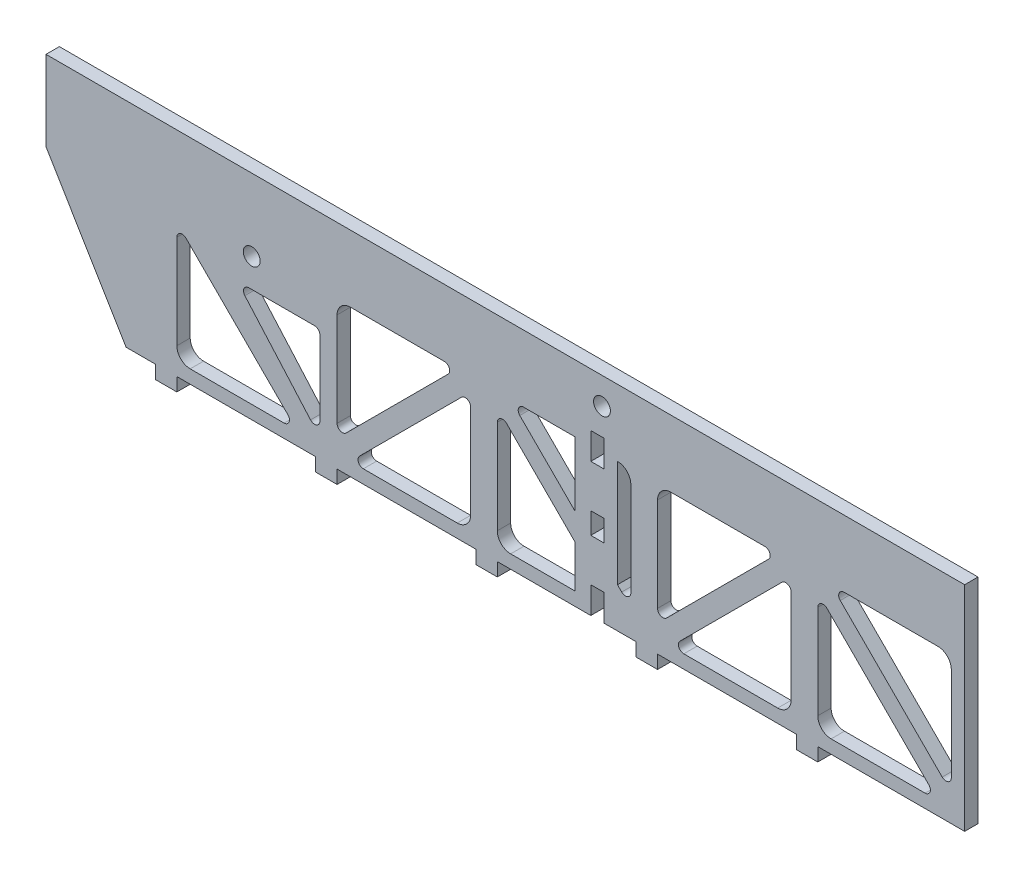
SolidWorks part; units mm, degrees
material "Pine"
ref_plane "Front Plane" through (0, 0, 0) normal (0, 0, 1) x (1, 0, 0)
ref_plane "Top Plane" through (0, 0, 0) normal (0, 1, 0) x (1, 0, 0)
ref_plane "Right Plane" through (0, 0, 0) normal (1, 0, 0) x (0, 0, -1)
sketch "Model" plane through (0, 0, 0) normal (0, 0, 1) x (1, 0, 0)
  line L0 (-306.6281, 15.625) -> (-306.6281, 51.1493)
  line L1 (-309.1681, 53.6893) -> (-340.406, 53.6893)
  line L2 (-342.3135, 49.472) -> (-311.0755, 13.9477)
  line L8 (-171.2321, 6.35) -> (-215.9, 6.35)
  line L9 (-222.25, 57.3679) -> (-222.25, 12.7)
  line L10 (-217.9139, 59.1639) -> (-169.4361, 10.6861)
  line L11 (-234.95, 57.3679) -> (-234.95, 12.7)
  line L12 (-241.3, 6.35) -> (-285.9679, 6.35)
  line L13 (-239.2861, 59.1639) -> (-287.7639, 10.6861)
  line L14 (-294.1139, 17.0361) -> (-245.6361, 65.5139)
  line L15 (-298.45, 63.5) -> (-298.45, 18.8321)
  line L16 (-247.4321, 69.85) -> (-292.1, 69.85)
  line L17 (-323.6321, 6.35) -> (-368.3, 6.35)
  line L18 (-374.65, 57.3679) -> (-374.65, 12.7)
  line L19 (-370.3139, 59.1639) -> (-321.8361, 10.6861)
  line L20 (-18.8321, 6.35) -> (-63.5, 6.35)
  line L21 (-69.85, 57.3679) -> (-69.85, 12.7)
  line L22 (-17.0361, 10.6861) -> (-65.5139, 59.1639)
  line L23 (-82.55, 57.3679) -> (-82.55, 12.7)
  line L24 (-88.9, 6.35) -> (-133.5679, 6.35)
  line L25 (-86.8861, 59.1639) -> (-135.3639, 10.6861)
  line L26 (-93.2361, 65.5139) -> (-141.7139, 17.0361)
  line L27 (-146.05, 63.5) -> (-146.05, 18.8321)
  line L28 (-95.0321, 69.85) -> (-139.7, 69.85)
  line L29 (-163.0861, 17.0361) -> (-211.5639, 65.5139)
  line L30 (-165.1, 69.85) -> (-209.7679, 69.85)
  line L31 (-158.75, 63.5) -> (-158.75, 18.8321)
  line L35 (-398.78, 0) -> (-436.88, 63.5)
  line L36 (0, 0) -> (-398.78, 0)
  line L37 (0, 0) -> (0, 95.25)
  line L38 (0, 95.25) -> (-436.88, 95.25)
  line L39 (-436.88, 63.5) -> (-436.88, 95.25)
  line L40 (-6.35, 63.5) -> (-6.35, 18.8321)
  line L41 (-59.1639, 65.5139) -> (-10.6861, 17.0361)
  line L42 (-12.7, 69.85) -> (-57.3679, 69.85)
  arc A0 (-222.25, 12.7) -> (-215.9, 6.35) centre (-215.9, 12.7) ccw
  arc A1 (-217.9139, 59.1639) -> (-222.25, 57.3679) centre (-219.71, 57.3679) ccw
  arc A2 (-171.2321, 6.35) -> (-169.4361, 10.6861) centre (-171.2321, 8.89) ccw
  arc A3 (-234.95, 57.3679) -> (-239.2861, 59.1639) centre (-237.49, 57.3679) ccw
  arc A4 (-241.3, 6.35) -> (-234.95, 12.7) centre (-241.3, 12.7) ccw
  arc A5 (-287.7639, 10.6861) -> (-285.9679, 6.35) centre (-285.9679, 8.89) ccw
  arc A6 (-245.6361, 65.5139) -> (-247.4321, 69.85) centre (-247.4321, 67.31) ccw
  arc A7 (-298.45, 18.8321) -> (-294.1139, 17.0361) centre (-295.91, 18.8321) ccw
  arc A8 (-292.1, 69.85) -> (-298.45, 63.5) centre (-292.1, 63.5) ccw
  arc A9 (-323.6321, 6.35) -> (-321.8361, 10.6861) centre (-323.6321, 8.89) ccw
  arc A10 (-374.65, 12.7) -> (-368.3, 6.35) centre (-368.3, 12.7) ccw
  arc A11 (-370.3139, 59.1639) -> (-374.65, 57.3679) centre (-372.11, 57.3679) ccw
  arc A12 (-69.85, 12.7) -> (-63.5, 6.35) centre (-63.5, 12.7) ccw
  arc A13 (-65.5139, 59.1639) -> (-69.85, 57.3679) centre (-67.31, 57.3679) ccw
  arc A14 (-18.8321, 6.35) -> (-17.0361, 10.6861) centre (-18.8321, 8.89) ccw
  arc A15 (-82.55, 57.3679) -> (-86.8861, 59.1639) centre (-85.09, 57.3679) ccw
  arc A16 (-88.9, 6.35) -> (-82.55, 12.7) centre (-88.9, 12.7) ccw
  arc A17 (-135.3639, 10.6861) -> (-133.5679, 6.35) centre (-133.5679, 8.89) ccw
  arc A18 (-93.2361, 65.5139) -> (-95.0321, 69.85) centre (-95.0321, 67.31) ccw
  arc A19 (-146.05, 18.8321) -> (-141.7139, 17.0361) centre (-143.51, 18.8321) ccw
  arc A20 (-139.7, 69.85) -> (-146.05, 63.5) centre (-139.7, 63.5) ccw
  arc A21 (-163.0861, 17.0361) -> (-158.75, 18.8321) centre (-161.29, 18.8321) ccw
  arc A22 (-209.7679, 69.85) -> (-211.5639, 65.5139) centre (-209.7679, 67.31) ccw
  arc A23 (-158.75, 63.5) -> (-165.1, 69.85) centre (-165.1, 63.5) ccw
  arc A24 (-306.6281, 15.625) -> (-311.0755, 13.9477) centre (-309.1681, 15.625) cw
  arc A25 (-340.406, 53.6893) -> (-342.3135, 49.472) centre (-340.406, 51.1493) ccw
  arc A26 (-306.6281, 51.1493) -> (-309.1681, 53.6893) centre (-309.1681, 51.1493) ccw
  arc A27 (-10.6861, 17.0361) -> (-6.35, 18.8321) centre (-8.89, 18.8321) ccw
  arc A28 (-57.3679, 69.85) -> (-59.1639, 65.5139) centre (-57.3679, 67.31) ccw
  arc A29 (-6.35, 63.5) -> (-12.7, 69.85) centre (-12.7, 63.5) ccw
  circle A30 centre (-172.466, 88.9) radius 4
  circle A32 centre (-172.466, 88.9) radius 167.9708 construction
  circle A33 centre (-339.0435, 67.31) radius 4
  dimension "D2" = 172.466
  dimension "D4" = 8
  dimension "D8" = 2.54
  dimension "D1" = 95.25
  dimension "D3" = 6.35
extrude "Boss-Extrude1" add sketch "Model" along normal blind 6.35
sketch "Sketch1" plane through (0, 0, 6.35) normal (0, 0, 1) x (1, 0, 0)
  line L0 (-69.85, 95.25) -> (-69.85, 0) construction
  line L1 (-69.85, 57.3679) -> (-69.85, 12.7) construction
  line L2 (-398.78, 0) -> (0, 0) construction
  line L3 (-146.05, 95.25) -> (-146.05, 0) construction
  line L4 (-146.05, 63.5) -> (-146.05, 18.8321) construction
  line L5 (-222.25, 95.25) -> (-222.25, 0) construction
  line L6 (-222.25, 57.3679) -> (-222.25, 12.7) construction
  line L7 (-298.45, 95.25) -> (-298.45, 0) construction
  line L8 (-298.45, 63.5) -> (-298.45, 18.8321) construction
  line L9 (-374.65, 95.25) -> (-374.65, 0) construction
  line L10 (-374.65, 57.3679) -> (-374.65, 12.7) construction
  line L11 (0, 95.25) -> (-436.88, 95.25) construction
  line L12 (-69.85, 0) -> (-80.01, 0)
  line L13 (-69.85, 0) -> (-69.85, -6.35)
  line L14 (-69.85, -6.35) -> (-80.01, -6.35)
  line L15 (-80.01, 0) -> (-80.01, -6.35)
  line L16 (-146.05, 0) -> (-156.21, 0)
  line L17 (-146.05, 0) -> (-146.05, -6.35)
  line L18 (-146.05, -6.35) -> (-156.21, -6.35)
  line L19 (-156.21, 0) -> (-156.21, -6.35)
  line L20 (-222.25, 0) -> (-232.41, 0)
  line L21 (-222.25, 0) -> (-222.25, -6.35)
  line L22 (-222.25, -6.35) -> (-232.41, -6.35)
  line L23 (-232.41, 0) -> (-232.41, -6.35)
  line L24 (-298.45, 0) -> (-308.61, 0)
  line L25 (-298.45, 0) -> (-298.45, -6.35)
  line L26 (-298.45, -6.35) -> (-308.61, -6.35)
  line L27 (-308.61, 0) -> (-308.61, -6.35)
  line L28 (-374.65, 0) -> (-384.81, 0)
  line L29 (-374.65, 0) -> (-374.65, -6.35)
  line L30 (-374.65, -6.35) -> (-384.81, -6.35)
  line L31 (-384.81, 0) -> (-384.81, -6.35)
  line L32 (0, 0) -> (0, 95.25) construction
  line L53 (-436.88, 95.25) -> (0, 95.25)
  line L54 (-436.88, 95.25) -> (-436.88, 101.6)
  line L55 (-436.88, 101.6) -> (0, 101.6)
  line L56 (0, 95.25) -> (0, 101.6)
  dimension "D1" = 6.35
  dimension "D2" = 10.16
  dimension "D3" = 10.16
  dimension "D4" = 10.16
  dimension "D5" = 10.16
  dimension "D6" = 10.16
  dimension "D8" = 6.35
extrude "Boss-Extrude2" add sketch "Sketch1" against normal up to surface (6.35 mm away) up to face at (-168.466, 88.9, 0)
sketch "Sketch2" plane through (0, 0, 0) normal (0, 0, -1) x (-1, 0, 0)
  line L0 (158.75, 18.8321) -> (158.75, 63.5) construction
  line L1 (185.42, 69.85) -> (165.1, 69.85)
  line L2 (185.42, 69.85) -> (185.42, 0)
  line L3 (185.42, 0) -> (165.1, 0)
  line L4 (165.1, 69.85) -> (165.1, 0)
  line L6 (222.25, 0) -> (156.21, 0) construction
  line L8 (165.1, 69.85) -> (209.7679, 69.85) construction
  line L10 (156.21, -6.35) -> (146.05, -6.35) construction
  line L11 (177.8, 0) -> (171.45, 0)
  line L12 (177.8, 0) -> (177.8, 12.7)
  line L13 (177.8, 12.7) -> (171.45, 12.7)
  line L14 (171.45, 0) -> (171.45, 12.7)
  line L15 (177.8, 33.02) -> (171.45, 33.02)
  line L16 (177.8, 33.02) -> (177.8, 43.18)
  line L17 (177.8, 43.18) -> (171.45, 43.18)
  line L18 (171.45, 33.02) -> (171.45, 43.18)
  line L19 (177.8, 63.5) -> (171.45, 63.5)
  line L20 (177.8, 63.5) -> (177.8, 76.2)
  line L21 (177.8, 76.2) -> (171.45, 76.2)
  line L22 (171.45, 63.5) -> (171.45, 76.2)
  dimension "D1" = 6.35
  dimension "D2" = 20.32
  dimension "D3" = 10.16
  dimension "D4" = 12.7
  dimension "D5" = 6.35
  dimension "D6" = 20.32
  dimension "D7" = 20.32
  dimension "D8" = 12.7
  dimension "D9" = 6.35
  dimension "D10" = 6.35
extrude "Boss-Extrude3" add sketch "Sketch2" against normal up to surface (6.35 mm away) contours L4 | L19 L22 L1 L4 L3 L14 L13 L12 L2 L20 L15 L18 L17 L16 region at (-184.6925, 34.925, 0) up to face at (-319.4123, 39.5294, 6.35)
extrude "Cut-Extrude1" cut sketch "Sketch2<3>" against normal blind 6.35 contours L22 L1 L20 L21 | L14 L3 L12 L13 region at (-174.625, 73.025, 0) region at (-174.625, 6.35, 0)
sketch "Sketch2<3>" plane through (0, 0, 0) normal (0, 0, -1) x (-1, 0, 0) same geometry as "Sketch2"
equation "\"thick\"=0.25"
equation "\"D1@Boss-Extrude1\"=\"thick\""
